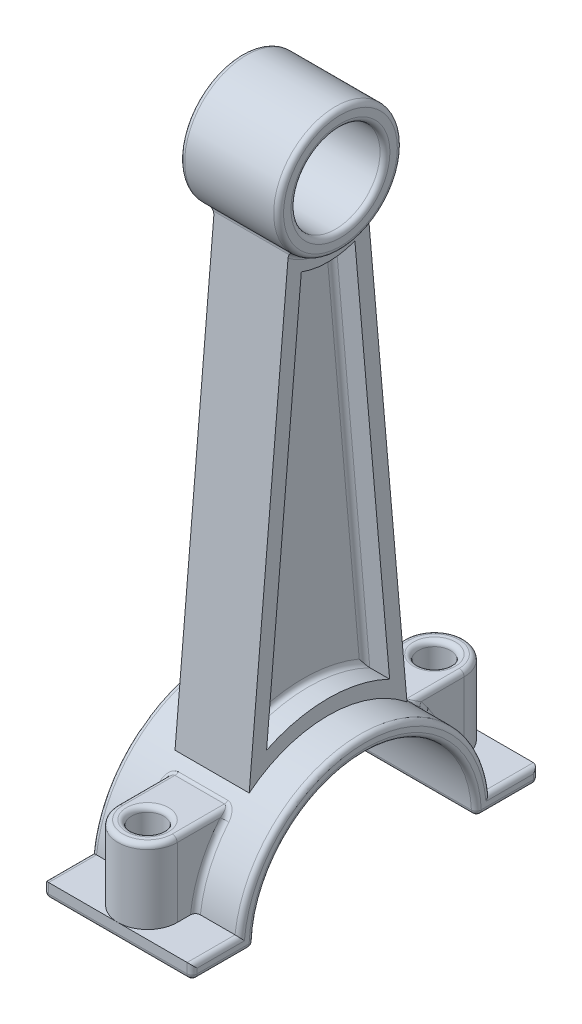
SolidWorks part; units mm, degrees
ref_plane "Front Plane" through (0, 0, 0) normal (0, 0, 1) x (1, 0, 0)
ref_plane "Top Plane" through (0, 0, 0) normal (0, 1, 0) x (1, 0, 0)
ref_plane "Right Plane" through (0, 0, 0) normal (1, 0, 0) x (0, 0, -1)
sketch "Sketch1" plane through (0, 0, 0) normal (1, 0, 0) x (0, 0, -1)
  line L0 (22.5, -120.4) -> (35, -120.4)
  line L1 (0, -120.4) -> (0, 0) construction
  line L2 (-22.5, -120.4) -> (-35, -120.4)
  line L3 (25.3229, -117.4) -> (35, -117.4)
  line L4 (-25.3229, -117.4) -> (-35, -117.4)
  line L5 (-35, -117.4) -> (-35, -120.4)
  line L6 (35, -117.4) -> (35, -120.4)
  line L7 (-8, -9.6047) -> (-15.9529, -100.5064)
  line L8 (8, -9.6047) -> (15.9529, -100.5064)
  circle A0 centre (0, 0) radius 9
  circle A1 centre (0, 0) radius 12.5
  arc A2 (22.5, -120.4) -> (-22.5, -120.4) centre (0, -120.4) ccw
  arc A3 (25.3229, -117.4) -> (-25.3229, -117.4) centre (0, -120.4) ccw
  point P18 (0, 0)
  point P19 (0, 0)
  dimension "D1" = 25
  dimension "D2" = 18
  dimension "D3" = 45
  dimension "D4" = 120.4
  dimension "D5" = 35
  dimension "D7" = 8
  dimension "D8" = 5
  dimension "D6" = 3
extrude "Boss-Extrude2" add sketch "Sketch1" along normal mid plane 20 contours A1
extrude "Boss-Extrude3" add sketch "Sketch1<9>" along normal mid plane 30 separate body contours A3 L4 L5 L2 A2 L0 L6 L3
sketch "Sketch1<9>" plane through (0, 0, 0) normal (1, 0, 0) x (0, 0, -1) same geometry as "Sketch1"
extrude "Boss-Extrude4" add sketch "Sketch1<12>" along normal mid plane 15 contours L1 A3 L8 A1 | A3 L1 A1 L7 region at (0, -58.5545, 6.2653) region at (0, -58.5545, -6.2653)
sketch "Sketch1<12>" plane through (0, 0, 0) normal (1, 0, 0) x (0, 0, -1) same geometry as "Sketch1"
extrude "Cut-Extrude1" cut sketch "Sketch1<13>" against normal through all both and the other way through all contours A0
sketch "Sketch1<13>" plane through (0, 0, 0) normal (1, 0, 0) x (0, 0, -1) same geometry as "Sketch1"
sketch "Sketch3" plane through (0, -117.4, 0) normal (0, 1, 0) x (1, 0, 0)
  line L0 (0, 35) -> (0, 19.8882) construction
  line L1 (15, 35) -> (-15, 35) construction
  line L3 (-4.7008, 35) -> (4.7008, 35)
  line L4 (-6, 29) -> (-6, 17)
  line L5 (-6, 17) -> (6, 17)
  line L6 (6, 29) -> (6, 17)
  arc A1 (6, 29) -> (-6, 29) centre (0, 29) ccw
  line M8 (-15, 25.3229) -> (15, 25.3229)
  dimension "D1" = 6
  dimension "D2" = 12
extrude "Boss-Extrude5" add sketch "Sketch3" along normal blind 15 contours A1 L0 L6 M8 | L4 L5 L6 A1 region at (2.7453, -117.4, -29.6245)
sketch "Sketch4" plane through (0, -102.4, 0) normal (0, 1, 0) x (1, 0, 0)
  circle A0 centre (0, 29) radius 3.25
  dimension "D1" = 6.5
extrude "Cut-Extrude2" cut sketch "Sketch4" against normal through all
mirror "Mirror1" about plane through (0, 0, 0) normal (0, 0, 1) of "Cut-Extrude2"
mirror "Mirror2" about plane through (0, 0, 0) normal (0, 0, 1) of "Boss-Extrude5"
mirror "Mirror3" about plane through (0, 0, 0) normal (0, 0, 1) of "Cut-Extrude2"
sketch "Sketch6" plane through (15, 0, 0) normal (1, 0, 0) x (0, 0, -1)
  line L0 (-22.5, -120.4) -> (22.5, -120.4)
  arc A0 (22.5, -120.4) -> (-22.5, -120.4) centre (0, -120.4) ccw construction
  arc A1 (22.5, -120.4) -> (-22.5, -120.4) centre (0, -120.4) ccw
extrude "Cut-Extrude4" cut sketch "Sketch6" against normal through all
sketch "Sketch7" plane through (7.5, 0, 0) normal (1, 0, 0) x (0, 0, -1)
  line L0 (-5.4187, -14.522) -> (-12.4385, -94.7576)
  line L1 (12.4385, -94.7576) -> (5.4187, -14.522)
  line L2 (-8, -9.6047) -> (-15.9529, -100.5064)
  line L3 (15.9529, -100.5064) -> (8, -9.6047)
  line L4 (-8, -9.6047) -> (-15.9529, -100.5064)
  line L5 (15.9529, -100.5064) -> (8, -9.6047)
  arc A0 (12.4385, -94.7576) -> (-12.4385, -94.7576) centre (0, -120.4) ccw
  arc A1 (-5.4187, -14.522) -> (5.4187, -14.522) centre (0, 0) ccw
  arc A2 (-8, -9.6047) -> (8, -9.6047) centre (0, 0) ccw
  arc A3 (15.9529, -100.5064) -> (-15.9529, -100.5064) centre (0, -120.4) ccw
  arc A4 (-8, -9.6047) -> (8, -9.6047) centre (0, 0) ccw
  arc A5 (15.9529, -100.5064) -> (-15.9529, -100.5064) centre (0, -120.4) ccw
  dimension "D1" = 0
  dimension "D2" = 3
extrude "Cut-Extrude5" cut sketch "Sketch7" against normal blind 5 contours L0 A0 L1 A1
sketch "Sketch8" plane through (-7.5, 0, 0) normal (-1, 0, 0) x (0, 0, 1)
  line L0 (-5.4187, -14.522) -> (-12.4385, -94.7576)
  line L1 (12.4385, -94.7576) -> (5.4187, -14.522)
  line L2 (-8, -9.6047) -> (-15.9529, -100.5064)
  line L3 (15.9529, -100.5064) -> (8, -9.6047)
  line L4 (-8, -9.6047) -> (-15.9529, -100.5064)
  line L5 (15.9529, -100.5064) -> (8, -9.6047)
  arc A0 (12.4385, -94.7576) -> (-12.4385, -94.7576) centre (0, -120.4) ccw
  arc A1 (-5.4187, -14.522) -> (5.4187, -14.522) centre (0, 0) ccw
  arc A2 (-8, -9.6047) -> (8, -9.6047) centre (0, 0) ccw
  arc A3 (15.9529, -100.5064) -> (-15.9529, -100.5064) centre (0, -120.4) ccw
  arc A4 (-8, -9.6047) -> (8, -9.6047) centre (0, 0) ccw
  arc A5 (15.9529, -100.5064) -> (-15.9529, -100.5064) centre (0, -120.4) ccw
  dimension "D1" = 0
  dimension "D2" = 3
extrude "Cut-Extrude6" cut sketch "Sketch8" against normal blind 5 contours L0 A0 L1 A1
fillet "Fillet1" radius 1 52 edges at (6, -109.2901, 22.9526) (-6, -109.2901, 22.9526) (-6, -109.2901, -22.9526) (6, -109.2901, -22.9526) (0, -120.4, -35) (0, -120.4, -25.75) (0, -120.4, 35) (0, -120.4, 25.75) (0, -120.4, 22.5) (0, -120.4, -22.5) (6, -102.4, 23.5312) (0, -102.4, 35) (-6, -102.4, 23.5312) (0, -102.4, 18.0624) (0, -102.4, 25.75) (-6, -102.4, -23.5312) (0, -102.4, -35) (6, -102.4, -23.5312) (0, -102.4, -18.0624) (0, -102.4, -25.75) (15, -118.9, -35) (15, -120.4, -28.75) (15, -97.9, 0) (15, -120.4, 28.75) (15, -118.9, 35) (15, -117.4, 30.1615) (15, -94.9, 0) (15, -117.4, -30.1615) (-15, -94.9, 0) (-15, -117.4, 30.1615) (-15, -118.9, 35) (-15, -120.4, 28.75) (-15, -97.9, 0) (-15, -120.4, -28.75) (-15, -118.9, -35) (-15, -117.4, -30.1615) (-2.5, -54.6398, 8.9286) (-2.5, -91.9, 0) (-2.5, -54.6398, -8.9286) (-2.5, -15.5, 0) (2.5, -54.6398, -8.9286) (2.5, -91.9, 0) (2.5, -54.6398, 8.9286) (2.5, -15.5, 0) (-10, 0, -9) (10, 0, -9) (-10, 0, -12.5) (10, 0, -12.5) (-7.5, -12.5, 0) (0, -9.6047, -8) (7.5, -12.5, 0) (0, -9.6047, 8)
